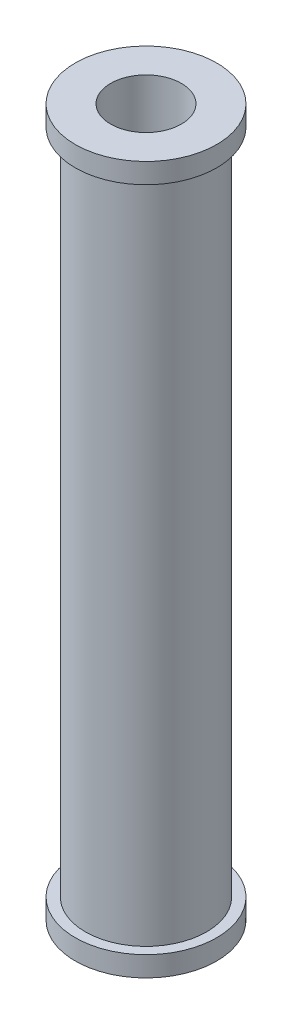
SolidWorks part; units mm, degrees
ref_plane "Front Plane" through (0, 0, 0) normal (0, 0, 1) x (1, 0, 0)
ref_plane "Top Plane" through (0, 0, 0) normal (0, 1, 0) x (1, 0, 0)
ref_plane "Right Plane" through (0, 0, 0) normal (1, 0, 0) x (0, 0, -1)
sketch "Sketch3" plane through (0, 0, 0) normal (0, 1, 0) x (1, 0, 0)
  circle A0 centre (0, 0) radius 3
  circle A1 centre (0, 0) radius 1.75
  dimension "D1" = 3.5
  dimension "D2" = 6
extrude "Boss-Extrude1" add sketch "Sketch3" along normal blind 33
sketch "Sketch19" plane through (0, 0, 0) normal (0, 0, 1) x (1, 0, 0)
  line L0 (0, 0) -> (0, 33)
  line L1 (3, 33) -> (-3, 33) construction
sketch "Sketch20" plane through (0, 0, 0) normal (0, 0, 1) x (1, 0, 0)
  circle A0 centre (3, 0) radius 0.5
  dimension "D1" = 1
sketch "Sketch21" plane through (0, 33, 0) normal (0, 1, 0) x (1, 0, 0)
  circle A0 centre (0, 0) radius 3.5
  dimension "D1" = 7
extrude "Boss-Extrude2" add sketch "Sketch21" along normal blind 1
sketch "Sketch29" plane through (0, 34, 0) normal (0, 1, 0) x (1, 0, 0)
  circle A0 centre (0, 0) radius 1.75
  circle A1 centre (0, 0) radius 3
  dimension "D1" = 6
  dimension "D2" = 3.5
extrude "Cut-Extrude6" cut sketch "Sketch29" against normal blind 8.3 contours A0
sketch "Sketch33" plane through (0, 0, 0) normal (0, -1, 0) x (1, 0, 0)
  circle A0 centre (0, 0) radius 3.5
  dimension "D1" = 7
extrude "Boss-Extrude5" add sketch "Sketch33" along normal blind 1
sketch "Sketch35" plane through (0, -1, 0) normal (0, -1, 0) x (1, 0, 0)
  circle A0 centre (0, 0) radius 1.75
  dimension "D1" = 3.5
extrude "Cut-Extrude8" cut sketch "Sketch35" against normal blind 1.3
